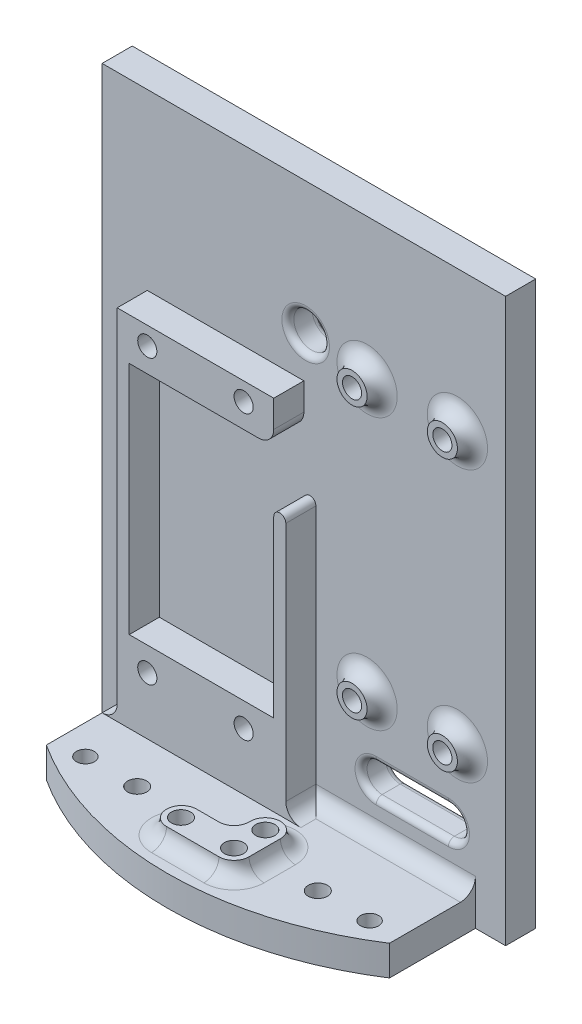
SolidWorks part; units mm, degrees
ref_plane "Front Plane" through (0, 0, 0) normal (0, 0, 1) x (1, 0, 0)
ref_plane "Top Plane" through (0, 0, 0) normal (0, 1, 0) x (1, 0, 0)
ref_plane "Right Plane" through (0, 0, 0) normal (1, 0, 0) x (0, 0, -1)
sketch "Sketch1" plane through (0, 0, 0) normal (0, 0, 1) x (1, 0, 0)
  line L1 (0, 0) -> (85.09, 0)
  line L2 (0, 0) -> (0, 118.618)
  line L3 (0, 118.618) -> (85.09, 118.618)
  line L4 (85.09, 0) -> (85.09, 118.618)
  dimension "D1" = 85.09
  dimension "D2" = 118.618
extrude "Boss1 - Main Plate" add sketch "Sketch1" along normal blind 6.35 contours L2 L1 L4 L3
sketch "Sketch3" plane through (0, 0, 0) normal (0, -1, 0) x (1, 0, 0)
  line L1 (0, 0) -> (85.09, 0) construction
  line L2 (6.35, 24.4739) -> (6.35, 0)
  line L3 (78.74, 24.4739) -> (78.74, 0)
  line L4 (0, 6.35) -> (0, 0) construction
  line L5 (85.09, 6.35) -> (85.09, 0) construction
  line L6 (6.35, 0) -> (78.74, 0)
  arc A0 (78.74, 24.4739) -> (6.35, 24.4739) centre (42.545, -31.5214) ccw
  dimension "D1" = 133.35
  dimension "D2" = 31.5214
  dimension "D3" = 42.545
  dimension "D4" = 6.35
  dimension "D5" = 6.35
  dimension "D6" = 0
extrude "Boss2 - Bottom Plate" add sketch "Sketch3" along direction (0, 1, 0) on the side against the normal blind 6.35
sketch "Sketch4" plane through (0, 0, 6.35) normal (0, 0, 1) x (1, 0, 0)
  line L0 (6.35, 6.35) -> (78.74, 6.35) construction
  line L1 (9.525, 6.35) -> (45.085, 6.35)
  line L2 (9.525, 6.35) -> (9.525, 23.495)
  line L3 (12.065, 23.495) -> (42.545, 23.495)
  line L4 (45.085, 6.35) -> (45.085, 23.495)
  line L7 (9.525, 23.495) -> (9.525, 73.025)
  line L9 (12.065, 23.495) -> (12.065, 73.025)
  line L11 (45.085, 23.495) -> (45.085, 60.325)
  line L13 (42.545, 23.495) -> (42.545, 60.325)
  line L14 (12.065, 73.025) -> (39.37, 73.025)
  line L15 (9.525, 73.025) -> (9.525, 81.915)
  line L16 (9.525, 81.915) -> (42.545, 81.915)
  line L17 (42.545, 76.2) -> (42.545, 81.915)
  arc A0 (39.37, 73.025) -> (42.545, 76.2) centre (39.37, 76.2) ccw
  arc A1 (45.085, 60.325) -> (42.545, 60.325) centre (43.815, 60.325) ccw
  dimension "D11" = 3.175
  dimension "D1" = 0
  dimension "D2" = 17.145
  dimension "D3" = 35.56
  dimension "D4" = 3.175
  dimension "D5" = 36.83
  dimension "D6" = 2.54
  dimension "D7" = 49.53
  dimension "D8" = 2.54
  dimension "D9" = 33.02
  dimension "D10" = 8.89
  dimension "D12" = 30.48
extrude "Boss3 - Battery Plate" add sketch "Sketch4" along normal blind 6.35
fillet "Fillet1 - Bottom Plate" radius 3.175 4 edges at (61.9125, 6.35, 6.35) (45.085, 6.35, 9.525) (9.525, 6.35, 9.525) (7.9375, 6.35, 6.35)
hole_wizard "Holes1 - CB Main Plate" positions "Sketch5" profile "Sketch6" hole size "1/4" standard "ANSI Inch" end condition through all
sketch "Sketch5" plane through (0, 0, 0) normal (0, 0, -1) x (-1, 0, 0)
  line L2 (0, 0) -> (0, 118.618) construction
  line L3 (0, 0) -> (-85.09, 0) construction
  point P8 (-36.195, 78.105)
  point P10 (-15.875, 78.105)
  point P12 (-15.875, 18.415)
  point P14 (-36.195, 18.415)
  dimension "D9" = 20.32
  dimension "D10" = 15.875
  dimension "D11" = 59.69
  dimension "D12" = 59.69
  dimension "D13" = 18.415
  dimension "D14" = 18.415
  dimension "D15" = 15.875
  dimension "D16" = 20.32
sketch "Sketch6" plane through (36.195, 78.105, 0) normal (1, 0, 0) x (0, 1, 0)
  line L0 (0, 0) -> (0, 35.1536)
  line L1 (0, 35.1536) -> (2.0193, 35.1536)
  line L2 (2.0193, 35.1536) -> (2.0193, 0)
  line L5 (2.0193, 0) -> (0, 0)
  line L11 (0, -6.35) -> (0, 107.95) construction
  dimension "Thru Hole Dia." = 4.0386
  dimension "Thru Hole Depth" = 35.1536
hole_wizard "Holes2 - Main Plate" positions "Sketch9" profile "Sketch8" hole size "1/4" standard "ANSI Inch" end condition through all
sketch "Sketch9" plane through (0, 0, 0) normal (0, 0, -1) x (-1, 0, 0)
  line L0 (0, 118.618) -> (-85.09, 118.618) construction
  line L1 (0, 0) -> (0, 118.618) construction
  point P0 (-42.926, 90.805)
  dimension "D1" = 27.813
  dimension "D2" = 42.926
sketch "Sketch8" plane through (42.926, 90.805, 0) normal (1, 0, 0) x (0, 1, 0)
  line L0 (0, 0) -> (0, 35.1536)
  line L1 (0, 35.1536) -> (3.7465, 35.1536)
  line L2 (3.7465, 35.1536) -> (3.7465, 0)
  line L5 (3.7465, 0) -> (0, 0)
  line L11 (0, -6.35) -> (0, 107.95) construction
  dimension "Thru Hole Dia." = 7.493
  dimension "Thru Hole Depth" = 35.1536
sketch "Sketch10" plane through (0, 0, 0) normal (0, 0, -1) x (-1, 0, 0)
  line L0 (0, 0) -> (-85.09, 0) construction
  line L1 (-73.025, 13.335) -> (-57.785, 13.335)
  line L3 (-73.025, 19.685) -> (-57.785, 19.685)
  line L5 (-85.09, 0) -> (-85.09, 118.618) construction
  arc A0 (-73.025, 19.685) -> (-73.025, 13.335) centre (-73.025, 16.51) ccw
  arc A1 (-57.785, 13.335) -> (-57.785, 19.685) centre (-57.785, 16.51) ccw
  dimension "D2" = 3.175
  dimension "D3" = 3.175
  dimension "D1" = 13.335
  dimension "D4" = 6.35
  dimension "D5" = 12.065
  dimension "D6" = 15.24
extrude "Cut1 - Main Plate" cut sketch "Sketch10" against normal up to surface (6.35 mm away) up to face at (46.6725, 90.805, 6.35)
fillet "Fillet2 - Main Plate Holes" radius 1.27 10 edges at (76.2, 16.51, 6.35) (65.405, 19.685, 6.35) (54.61, 16.51, 6.35) (54.61, 16.51, 0) (65.405, 13.335, 0) (76.2, 16.51, 0) (39.1795, 90.805, 0) (46.6725, 90.805, 6.35) (65.405, 13.335, 6.35) (65.405, 19.685, 0)
hole_wizard "Holes3 - Bottom Plate" positions "Sketch11" profile "Sketch12" hole size "1/4" standard "ANSI Inch" end condition through all
sketch "Sketch11" plane through (0, 0, 0) normal (0, -1, 0) x (-1, 0, 0)
  line L0 (0, 0) -> (-85.09, 0) construction
  line L1 (-6.35, -24.4739) -> (-6.35, -6.35) construction
  line L2 (-78.74, -6.35) -> (-78.74, -24.4739) construction
  point P0 (-23.495, -22.4536)
  point P2 (-61.595, -22.4536)
  dimension "D1" = 22.4536
  dimension "D2" = 22.4536
  dimension "D3" = 17.145
  dimension "D4" = 17.145
sketch "Sketch12" plane through (23.495, 0, 22.4536) normal (1, 0, 0) x (0, 0, -1)
  line L0 (0, 0) -> (0, 118.618)
  line L1 (0, 118.618) -> (2.0193, 118.618)
  line L2 (2.0193, 118.618) -> (2.0193, 0)
  line L5 (2.0193, 0) -> (0, 0)
  line L11 (0, -6.35) -> (0, 107.95) construction
  dimension "Thru Hole Dia." = 4.0386
  dimension "Thru Hole Depth" = 118.618
sketch "Sketch14" plane through (0, 0, 6.35) normal (0, 0, 1) x (1, 0, 0)
  line L0 (0, 118.618) -> (85.09, 118.618) construction
  line L2 (85.09, 0) -> (85.09, 118.618) construction
  circle A0 centre (55.88, 88.9) radius 3.175
  circle A1 centre (74.93, 88.9) radius 3.175
  circle A2 centre (55.88, 31.75) radius 3.175
  circle A3 centre (74.93, 31.75) radius 3.175
  point P0 (55.88, 88.9)
  point P1 (74.93, 88.9)
  point P2 (55.88, 31.75)
  point P3 (74.93, 31.75)
  dimension "D9" = 6.35
  dimension "D10" = 6.35
  dimension "D11" = 6.35
  dimension "D12" = 6.35
  dimension "D1" = 29.718
  dimension "D2" = 29.718
  dimension "D3" = 57.15
  dimension "D4" = 57.15
  dimension "D5" = 10.16
  dimension "D6" = 10.16
  dimension "D7" = 19.05
  dimension "D8" = 19.05
extrude "Boss4 - Main Plate Standoff" add sketch "Sketch14" along direction (0, 0, -1) on the side of the normal offset from surface (3.175 mm away) 3.175 up to face at (47.9425, 90.805, 6.35) offset beyond the face yes
sketch "Hole Position Sketch 1" plane through (0, 0, 9.525) normal (0, 0, 1) x (1, 0, 0)
  point P0 (55.88, 88.9)
  point P1 (74.93, 88.9)
  point P3 (55.88, 31.75)
  point P5 (74.93, 31.75)
hole_wizard "Holes5 - Main Plate" positions "Sketch16" profile "Sketch17" hole size "1/4" standard "ANSI Inch" end condition through all
sketch "Sketch16" plane through (0, 0, 9.525) normal (0, 0, 1) x (1, 0, 0)
  point P0 (55.88, 88.9)
  point P3 (74.93, 88.9)
  point P6 (55.88, 31.75)
  point P9 (74.93, 31.75)
sketch "Sketch17" plane through (55.88, 88.9, 9.525) normal (1, 0, 0) x (0, -1, 0)
  line L0 (0, 0) -> (0, 9.525)
  line L1 (0, 9.525) -> (2.0193, 9.525)
  line L2 (2.0193, 9.525) -> (2.0193, 0)
  line L5 (2.0193, 0) -> (0, 0)
  line L11 (0, -6.35) -> (0, 107.95) construction
  dimension "Thru Hole Dia." = 4.0386
  dimension "Thru Hole Depth" = 9.525
fillet "Fillet3 - Main Plate Standoff" radius 3.175 4 edges at (59.055, 31.75, 6.35) (78.105, 31.75, 6.35) (59.055, 88.9, 6.35) (78.105, 88.9, 6.35)
sketch "Hole Position Sketch 2" plane through (0, 0, 0) normal (0, -1, 0) x (1, 0, 0)
  line L0 (0, 0) -> (85.09, 0) construction
  line L1 (6.35, 24.4739) -> (6.35, 6.35) construction
  line L2 (78.74, 6.35) -> (78.74, 24.4739) construction
  point P0 (48.133, 26.67)
  point P1 (48.133, 20.066)
  point P2 (36.957, 26.67)
  dimension "D1" = 26.67
  dimension "D2" = 30.607
  dimension "D3" = 20.066
  dimension "D4" = 6.604
  dimension "D5" = 30.607
  dimension "D6" = 30.607
sketch "Sketch21" plane through (0, 6.35, 0) normal (0, 1, 0) x (1, 0, 0)
  line L0 (37.084, -23.495) -> (41.783, -23.495)
  line L1 (37.084, -29.845) -> (48.133, -29.845)
  line L2 (44.958, -20.066) -> (44.958, -20.32)
  line L3 (51.308, -20.066) -> (51.308, -26.67)
  line L4 (78.74, -9.525) -> (78.74, -24.4739) construction
  arc A0 (37.084, -23.495) -> (37.084, -29.845) centre (37.084, -26.67) ccw
  arc A1 (48.133, -29.845) -> (51.308, -26.67) centre (48.133, -26.67) ccw
  arc A2 (51.308, -20.066) -> (44.958, -20.066) centre (48.133, -20.066) ccw
  arc A3 (44.958, -20.32) -> (41.783, -23.495) centre (41.783, -20.32) cw
  point P0 (36.957, -26.67)
  point P1 (48.133, -26.67)
  point P3 (48.133, -20.066)
  dimension "D2" = 3.175
  dimension "D3" = 3.175
  dimension "D9" = 3.175
  dimension "D1" = 3.175
  dimension "D4" = 3.175
  dimension "D5" = 3.175
  dimension "D6" = 0
  dimension "D7" = 0
  dimension "D8" = 41.656
extrude "Boss5 - Bottom Plate Standoff" add sketch "Sketch21" along direction (0, -1, 0) on the side of the normal offset from surface (3.175 mm away) 3.175 up to face at (23.495, 6.35, 20.4343) offset beyond the face yes
fillet "Fillet4 - Bottom Plate Standoff" radius 3.175 8 edges at (39.4335, 6.35, 23.495) (44.0281, 6.35, 22.5651) (44.958, 6.35, 20.193) (48.133, 6.35, 16.891) (51.308, 6.35, 23.368) (50.3781, 6.35, 28.9151) (33.909, 6.35, 26.67) (42.6085, 6.35, 29.845)
hole_wizard "Holes6 - Bottom Plate" positions "Sketch23" profile "Sketch24" hole size "1/4" standard "ANSI Inch" end condition through all
sketch "Sketch23" plane through (0, 0, 0) normal (0, -1, 0) x (-1, 0, 0)
  point P0 (-36.957, -26.67)
  point P3 (-48.133, -26.67)
  point P6 (-48.133, -20.066)
sketch "Sketch24" plane through (36.957, 0, 26.67) normal (1, 0, 0) x (0, 0, -1)
  line L0 (0, 0) -> (0, 118.618)
  line L1 (0, 118.618) -> (2.0193, 118.618)
  line L2 (2.0193, 118.618) -> (2.0193, 0)
  line L5 (2.0193, 0) -> (0, 0)
  line L11 (0, -6.35) -> (0, 107.95) construction
  dimension "Thru Hole Dia." = 4.0386
  dimension "Thru Hole Depth" = 118.618
hole_wizard "Holes7" positions "Sketch25" profile "Sketch26" hole size "#6" standard "ANSI Inch" end condition through all
sketch "Sketch25" plane through (0, 6.35, 0) normal (0, 1, 0) x (1, 0, 0)
  circle A0 centre (23.495, -22.4536) radius 2.0193 construction
  circle A1 centre (61.595, -22.4536) radius 2.0193 construction
  point P0 (72.517, -22.4536)
  point P2 (12.573, -22.4536)
  dimension "D1" = 10.922
  dimension "D2" = 10.922
  dimension "D3" = 0
  dimension "D4" = 0
sketch "Sketch26" plane through (72.517, 6.35, 22.4536) normal (1, 0, 0) x (0, 0, 1)
  line L0 (0, 0) -> (0, 6.35)
  line L1 (0, 6.35) -> (1.8986, 6.35)
  line L2 (1.8986, 6.35) -> (1.8986, 0)
  line L5 (1.8986, 0) -> (0, 0)
  line L11 (0, -6.35) -> (0, 107.95) construction
  dimension "Thru Hole Dia." = 3.7973
  dimension "Thru Hole Depth" = 6.35
equation "\"D12@Sketch5\"=\"D11@Sketch5\""
equation "\"D14@Sketch5\"=\"D13@Sketch5\""
equation "\"D15@Sketch5\"=\"D10@Sketch5\""
equation "\"D16@Sketch5\"=\"D9@Sketch5\""
equation "\"D3@Sketch10\"=\"D2@Sketch10\""
equation "\"D2@Sketch11\"=\"D1@Sketch11\""
equation "\"D2@Sketch14\"=\"D1@Sketch14\""
equation "\"D4@Sketch14\"=\"D3@Sketch14\""
equation "\"D6@Sketch14\"=\"D5@Sketch14\""
equation "\"D8@Sketch14\"=\"D7@Sketch14\""
equation "\"D10@Sketch14\"=\"D9@Sketch14\""
equation "\"D11@Sketch14\"=\"D9@Sketch14\""
equation "\"D12@Sketch14\"=\"D10@Sketch14\""
equation "\"D6@Hole Position Sketch 2\"=\"D5@Hole Position Sketch 2\""
equation "\"D2@Sketch21\"=\"D1@Sketch21\""
equation "\"D3@Sketch21\"=\"D2@Sketch21\""
equation "\"D5@Sketch21\"=\"D1@Sketch21\""
equation "\"D2@Hole Position Sketch 2\"=\"D5@Hole Position Sketch 2\""
